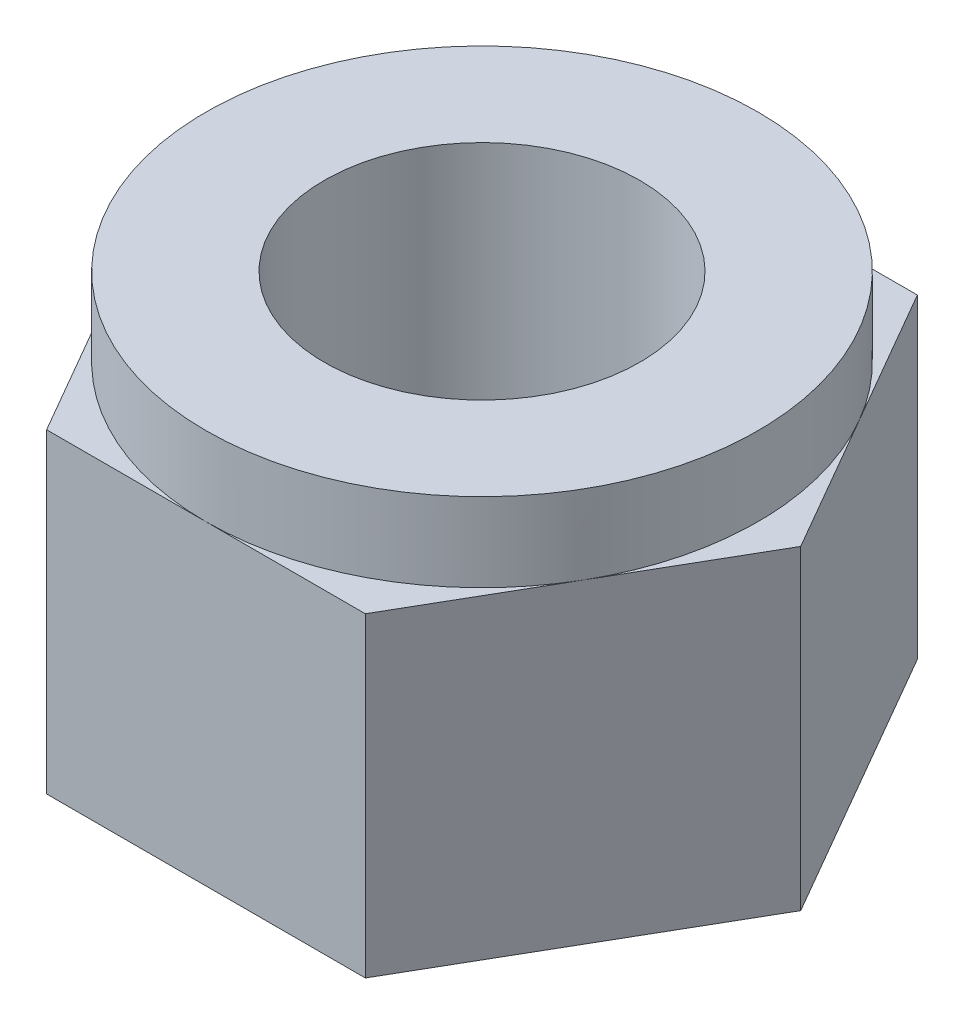
SolidWorks part; units mm, degrees
ref_plane "前视基准面" through (0, 0, 0) normal (0, 0, 1) x (1, 0, 0)
ref_plane "上视基准面" through (0, 0, 0) normal (0, 1, 0) x (1, 0, 0)
ref_plane "右视基准面" through (0, 0, 0) normal (1, 0, 0) x (0, 0, -1)
other "Configuration Table"
sketch "草图1" plane through (0, 0, 0) normal (0, 1, 0) x (1, 0, 0)
  line L1 (4.0415, 0) -> (2.0207, 3.5)
  line L2 (2.0207, 3.5) -> (-2.0207, 3.5)
  line L3 (-2.0207, 3.5) -> (-4.0415, 0)
  line L4 (-4.0415, 0) -> (-2.0207, -3.5)
  line L5 (-2.0207, -3.5) -> (2.0207, -3.5)
  line L6 (2.0207, -3.5) -> (4.0415, 0)
  circle A0 centre (0, 0) radius 3.5 construction
  dimension "D1" = 7
extrude "凸台-拉伸1" add sketch "草图1" along normal blind 4
sketch "草图2" plane through (0, 4, 0) normal (0, 1, 0) x (1, 0, 0)
  line L0 (2.0207, -3.5) -> (4.0415, 0) construction
  circle A0 centre (0, 0) radius 3.5
extrude "凸台-拉伸2" add sketch "草图2" along normal blind 1
sketch "草图3" plane through (0, 0, 0) normal (0, -1, 0) x (1, 0, 0)
  circle A0 centre (0, 0) radius 2
  dimension "D1" = 4
extrude "切除-拉伸1" cut sketch "草图3" against normal through all
ref_axis "基准轴1" through (0, 8.2881, 0) along (0, -1, 0)
